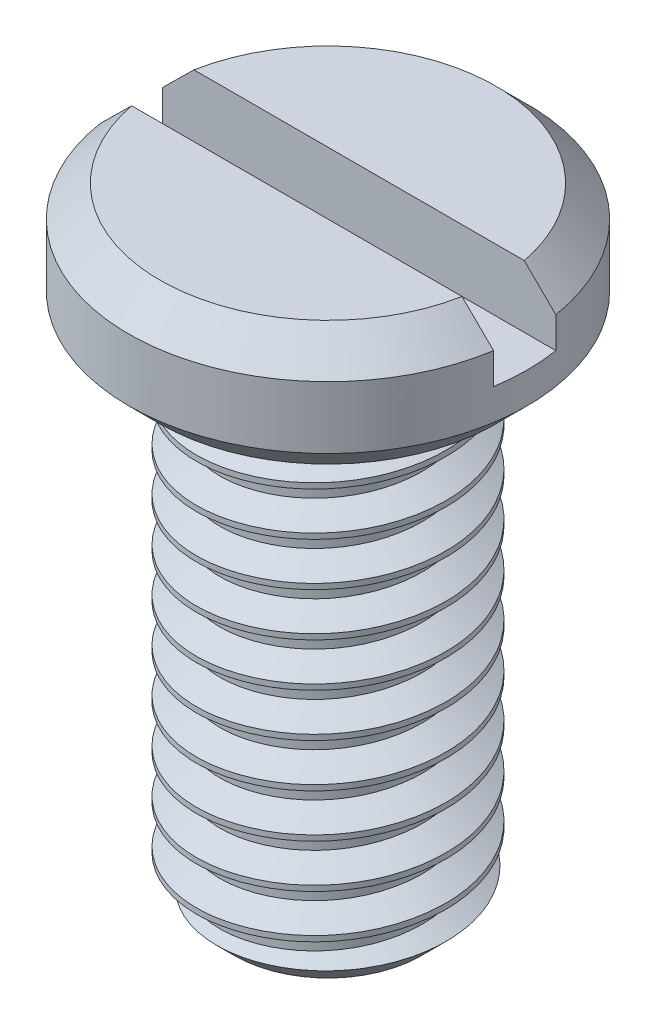
SolidWorks part; units mm, degrees
ref_plane "Front" through (0, 0, 0) normal (0, 0, 1) x (1, 0, 0)
ref_plane "Top" through (0, 0, 0) normal (0, 1, 0) x (1, 0, 0)
ref_plane "Right" through (0, 0, 0) normal (1, 0, 0) x (0, 0, -1)
sketch "Sketch1" plane through (0, 0, 0) normal (0, 1, 0) x (1, 0, 0)
  circle A0 centre (0, 0) radius 2
extrude "Boss-Extrude1" add sketch "Sketch1" along normal blind 8
chamfer "Chamfer1" distance 0.5 angle 45 1 edges at (0, 0, 2)
thread "Thread1" pitch 0.7 method cut profile "Thread Profile1" start angle 0, offset 1, length 10, pitch 0.7, diameter 4
ref_plane "Plane1" through (-2, 9, 0) normal (0, 0, 1) x (-1, 0, 0)
sketch "Thread Profile1" plane through (-2, 9, 0) normal (0, 0, 1) x (-1, 0, 0)
  line L0 (0, 0) -> (0, 0.7) construction
  line L11 (0, 0) -> (0, 0.6125)
  line L12 (0, 0.6125) -> (-0.3789, 0.3937)
  line L13 (-0.3789, 0.3937) -> (-0.3789, 0.2187)
  line L15 (-0.3789, 0.2187) -> (0, 0)
  line L17 (-0.3789, 0.3062) -> (0, 0.3062) construction
  point P2 (0, 0)
  dimension "Pitch" = 0.7
  dimension "Profile_Angle" = 60
  dimension "Profile_Land" = 0.175
  dimension "Profile_Height" = 0.3789
sketch "Sketch4" plane through (0, 8, 0) normal (0, 1, 0) x (1, 0, 0)
  circle A0 centre (0, 0) radius 3.2
extrude "Boss-Extrude2" add sketch "Sketch4" along normal blind 2
chamfer "Chamfer2" distance 0.5 angle 45 2 edges at (0, 10, 3.2) (0, 8, 3.2)
sketch "Sketch5" plane through (0, 10, 0) normal (0, 1, 0) x (1, 0, 0)
  line L0 (-4.5904, 0) -> (3.6091, 0) construction
  line L2 (-3.5409, -0.5) -> (3.5409, -0.5)
  line L3 (-3.5409, -0.5) -> (-3.5409, 0.5)
  line L4 (-3.5409, 0.5) -> (3.5409, 0.5)
  line L5 (3.5409, -0.5) -> (3.5409, 0.5)
  line L6 (-3.5409, -0.5) -> (3.5409, 0.5) construction
  line L7 (-3.5409, 0.5) -> (3.5409, -0.5) construction
  point P3 (0, 0)
extrude "Cut-Extrude1" cut sketch "Sketch5" against normal blind 1
